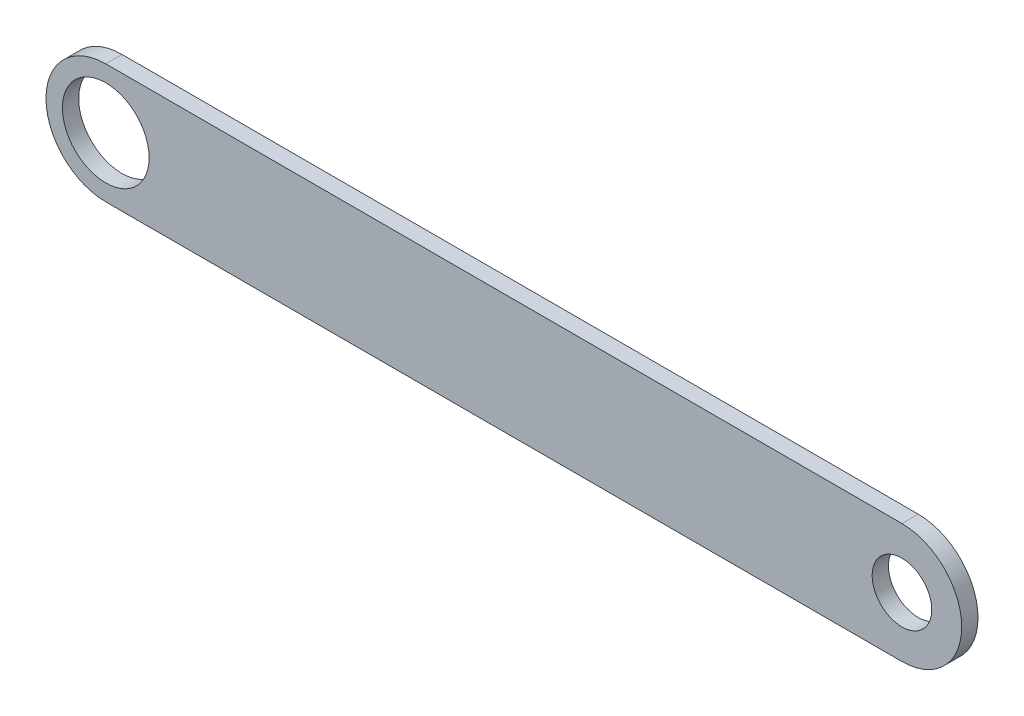
SolidWorks part; units mm, degrees
material "Cast Alloy Steel"
ref_plane "Front Plane" through (0, 0, 0) normal (0, 0, 1) x (1, 0, 0)
ref_plane "Top Plane" through (0, 0, 0) normal (0, 1, 0) x (1, 0, 0)
ref_plane "Right Plane" through (0, 0, 0) normal (1, 0, 0) x (0, 0, -1)
sketch "Sketch1" plane through (0, 0, 0) normal (0, 0, 1) x (1, 0, 0)
  line L0 (-73.275, 0) -> (73.275, 0) construction
  line L1 (-73.275, 11) -> (73.275, 11)
  line L2 (-73.275, -11) -> (73.275, -11)
  line L3 (0, 31.5598) -> (0, -22.2851) construction
  arc A0 (-73.275, 11) -> (-73.275, -11) centre (-73.275, 0) ccw
  arc A1 (73.275, -11) -> (73.275, 11) centre (73.275, 0) ccw
  circle A2 centre (-73.275, 0) radius 7.985
  circle A3 centre (73.275, 0) radius 5.485
  point P3 (0, 0)
  dimension "D1" = 15.97
  dimension "D2" = 11
  dimension "D3" = 146.55
  dimension "D4" = 10.97
extrude "Boss-Extrude1" add sketch "Sketch1" along normal blind 3
